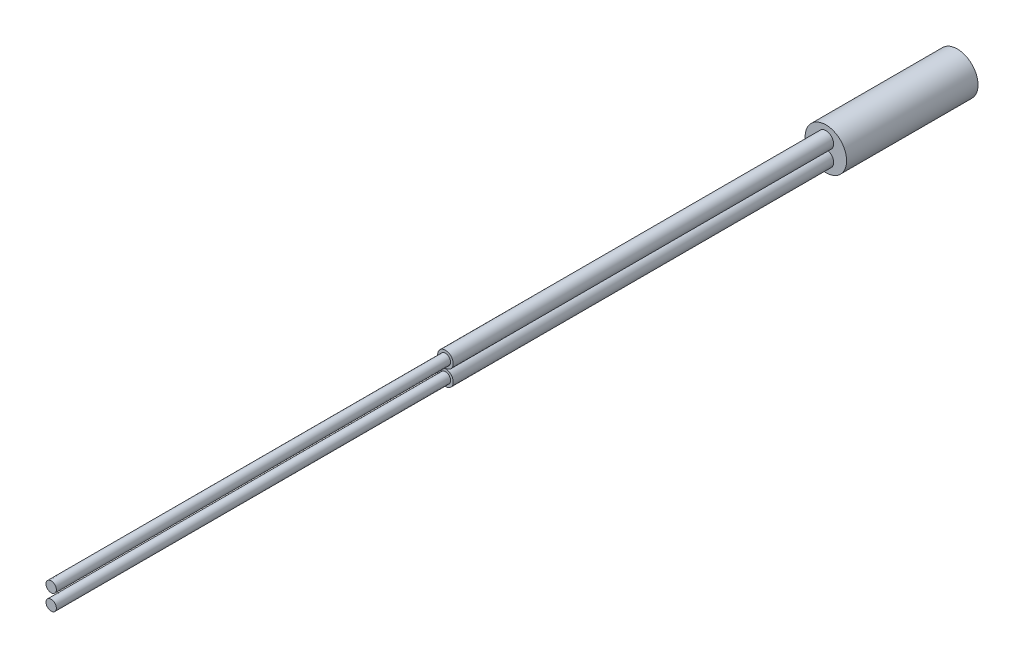
SolidWorks part; units mm, degrees
material "acero"
ref_plane "Alzado" through (0, 0, 0) normal (0, 0, 1) x (1, 0, 0)
ref_plane "Planta" through (0, 0, 0) normal (0, 1, 0) x (1, 0, 0)
ref_plane "Vista lateral" through (0, 0, 0) normal (1, 0, 0) x (0, 0, -1)
sketch "Croquis1" plane through (0, 0, 0) normal (0, 0, 1) x (1, 0, 0)
  circle A0 centre (0, 0) radius 3
  dimension "D1" = 6
extrude "Saliente-Extruir1" add sketch "Croquis1" along normal blind 18
ref_plane "Plano1" through (0, 0.5, 0) normal (0, -1, 0) x (-1, 0, 0)
ref_plane "Plano2" through (0, -9.5, 0) normal (0, -1, 0) x (-1, 0, 0)
ref_plane "Plano3" through (-23.0763, 0, 10.7606) normal (-0.9063, 0, 0.4226) x (0.4226, 0, 0.9063)
sketch3d "Croquis3D1"
  line L0 (0, 0, 18) -> (0, 0, 21)
  line L1 (0, 0, 18) -> (0, 0, 0) construction
  line L2 (-17.166, -4.6752, 23.4353) -> (-17.166, -8.5854, 23.4353)
  line L3 (-6.75, -14.9111, 10) -> (-6.75, 16.5741, 10) construction
  spline S0 degree 3 poles (0, 0, 21) (0, 0, 27.5004) (-12.019, 3.2907, 25.754) (-17.166, -2.2029, 23.4353) (-17.166, -4.6752, 23.4353) knots 0 0 0 0 0.663423 1 1 1 1
  dimension "D1" = 17
  dimension "D2" = 3
sketch "Croquis2" plane through (0, 0, 18) normal (0, 0, 1) x (1, 0, 0)
  circle A0 centre (0, 0) radius 0.8 construction
  circle A1 centre (-0.8, 0) radius 0.75
  circle A2 centre (0.8, 0) radius 0.75
  dimension "D1" = 1.6
  dimension "D2" = 1.5
sweep "Barrer1" [suppressed] add profiles "Croquis2" path "Croquis3D1"
extrude "Saliente-Extruir2" add sketch "Croquis1<2>" along normal blind 21.5 and the other way blind 1.5
sketch "Croquis1<2>" plane through (0, 0, 0) normal (0, 0, 1) x (1, 0, 0) same geometry as "Croquis1"
sketch "Croquis3" plane through (0, 0, -1.5) normal (0, 0, -1) x (-1, 0, 0)
  circle A0 centre (0, 0) radius 3
  dimension "D1" = 6
extrude "Cortar-Extruir1" cut sketch "Croquis3" against normal blind 4
sketch "Croquis4" plane through (0, 0, 0) normal (1, 0, 0) x (0, 0, -1)
  line L0 (-18.6464, 0) -> (-2.5, 0) construction
  line L1 (-2.5, -3) -> (-2.5, 3) construction
  line L2 (-2.5, 0) -> (8.1511, 15.6197) construction
  dimension "D1" = 34.29
sketch3d "Croquis3D4"
  line L0 (0, 0, 2.5) -> (-18.9322, 0, 2.5) construction
ref_plane "Plano4" through (0, 1.1637, 1.7065) normal (0, -0.5634, -0.8262) x (-1, 0, 0)
sketch3d "Croquis3D3" [suppressed]
  line L0 (-1.9716, 13.6377, 26.3138) -> (-2.2072, 8.1317, 30.0679)
  line L1 (-5.6206, 5.0135, 32.2682) -> (-41.5, -3.146, 34.1262)
  line L2 (-47.8249, -2.5398, 38.3697) -> (-47.8249, -22.8208, 52.1977)
  line L3 (-43.8249, -26.1257, 54.4511) -> (-27.8372, -26.1257, 54.4511)
  line L4 (-41, -0.2448, 33.0559) -> (-27.23, 0.0992, 33.3873)
  line L5 (-27.23, 0.0992, 33.3873) -> (-27.23, 3.5226, 33.3873)
  line L6 (-27.23, 3.5226, 33.3873) -> (-1.9922, 3.5226, 33.3873)
ref_plane "Plano5" through (0, 16.9384, 24.84) normal (0, -0.5634, -0.8262) x (-1, 0, 0)
sketch "Croquis6" plane through (0, 16.9384, 24.84) normal (0, -0.5634, -0.8262) x (-1, 0, 0)
  line L0 (0, -15.6127) -> (0, -12.1127) construction
  line L1 (22, -19.1127) -> (22, -15.6127)
  line L4 (22, -15.6127) -> (0, -15.6127)
  line L5 (47.5, -19.1127) -> (22, -19.1127)
  line L6 (47.5, -19.1127) -> (47.5, -50.6127)
  line L7 (47.5, -50.6127) -> (33.5, -50.6127)
  ellipse E0 centre (0, -12.1127) end of major axis (-3, -12.1127) minor radius 2.4786 construction
  dimension "D1" = 38.5
  dimension "D2" = 47.5
  dimension "D3" = 7
  dimension "D4" = 3.5
  dimension "D5" = 22
  dimension "D6" = 14
sketch3d "Croquis3D5"
  line L0 (0, 0, 21.5) -> (0, 4.0392, 33.6359) construction
  line L1 (0, 0, 21.5) -> (0, 0, 2.5) construction
  line L2 (-22, 3.2001, 34.2081) -> (-21.2499, 4.0392, 33.6359) construction
  line L3 (-47.5, -24.8777, 53.3543) -> (-33.5, -24.8777, 53.3543) construction
  line L4 (-47.5, 1.1475, 35.6078) -> (-47.5, -24.8777, 53.3543) construction
  line L5 (-44.5, -24.8777, 53.3543) -> (-47.5, -22.3991, 51.6641) construction
  line L6 (-46.4717, -0.2698, 36.5742) -> (-45.5, 1.1475, 35.6078) construction
  line L7 (-47.5, 1.1475, 35.6078) -> (-22, 1.1475, 35.6078) construction
  line L8 (-22, 1.1475, 35.6078) -> (-22, 4.0392, 33.6359) construction
  line L9 (-22.8792, 1.1475, 35.6078) -> (-22, 1.873, 35.113) construction
  line L10 (-22, 4.0392, 33.6359) -> (0, 4.0392, 33.6359) construction
  line L11 (-2, 4.0392, 33.6359) -> (0, 3.4076, 31.7383) construction
  arc A0 (-42.3787, -24.8777, 53.3543) -> (-47.5, -20.6465, 50.469) centre (-42.3787, -20.6465, 50.469) cw
  arc A1 (-47.5, -2.1436, 37.852) -> (-43.5165, 1.1475, 35.6078) centre (-43.5165, -2.1436, 37.852) cw
  arc A2 (-23.5, 1.1475, 35.6078) -> (-22, 2.3868, 34.7627) centre (-23.5, 2.3868, 34.7627) cw
  arc A4 (-3.4142, 4.0392, 33.6359) -> (0, 2.961, 30.3964) centre (-3.4142, 2.961, 30.3964) cw
  arc A5 (-22, 2.7999, 34.481) -> (-20.5, 4.0392, 33.6359) centre (-20.5, 2.7999, 34.481) cw
  point P7 (-42.3787, -23.5317, 46.2378)
  point P16 (-46, -23.6384, 52.5092)
  point P25 (-43.5165, -4.3879, 34.5608)
  point P27 (-45.9859, 0.4389, 36.091)
  point P29 (-23.5, 3.2319, 36.002)
  point P31 (-22.4396, 1.5102, 35.3604)
  point P44 (-20.5, 1.9548, 33.2417)
  point P46 (-21.625, 3.6196, 33.922)
  point P51 (-3.4142, 6.2005, 29.3182)
  point P53 (-1, 3.7234, 32.6871)
  dimension "D5" = 1.5
  dimension "D2" = 3
  dimension "D11" = 3
  dimension "D3" = 2
  dimension "D4" = 2
  dimension "D7" = 1.5
  dimension "D9" = 2
  dimension "D10" = 2
sketch3d "Croquis3D7"
  line L0 (-47.5, -24.8777, 53.3543) -> (-33.5, -24.8777, 53.3543) construction
  line L1 (-47.5, 1.1475, 35.6078) -> (-47.5, -24.8777, 53.3543) construction
  line L2 (-47.5, 1.1475, 35.6078) -> (-22, 1.1475, 35.6078) construction
  line L3 (-22, 1.1475, 35.6078) -> (-22, 4.0392, 33.6359) construction
  line L4 (-22, 4.0392, 33.6359) -> (0, 4.0392, 33.6359) construction
  line L5 (0, 0, 21.5) -> (0, 4.0392, 33.6359) construction
  line L6 (-42.3787, -24.8777, 53.3543) -> (-33.5, -24.8777, 53.3543)
  line L7 (-47.5, -2.1436, 37.852) -> (-47.5, -20.6465, 50.469)
  line L8 (-43.5165, 1.1475, 35.6078) -> (-23.5, 1.1475, 35.6078)
  line L9 (-22, 2.3868, 34.7627) -> (-22, 2.7999, 34.481)
  line L10 (-20.5, 4.0392, 33.6359) -> (-3.4142, 4.0392, 33.6359)
  line L11 (0, 0, 21.5) -> (0, 2.961, 30.3964)
  arc A0 (-42.3787, -24.8777, 53.3543) -> (-47.5, -20.6465, 50.469) centre (-42.3787, -20.6465, 50.469) ccw construction
  arc A1 (-47.5, -2.1436, 37.852) -> (-43.5165, 1.1475, 35.6078) centre (-43.5165, -2.1436, 37.852) ccw construction
  arc A2 (-23.5, 1.1475, 35.6078) -> (-22, 2.3868, 34.7627) centre (-23.5, 2.3868, 34.7627) ccw construction
  arc A4 (-3.4142, 4.0392, 33.6359) -> (0, 2.961, 30.3964) centre (-3.4142, 2.961, 30.3964) ccw construction
  arc A5 (-42.3787, -24.8777, 53.3543) -> (-47.5, -20.6465, 50.469) centre (-42.3787, -20.6465, 50.469) ccw
  arc A6 (-47.5, -2.1436, 37.852) -> (-43.5165, 1.1475, 35.6078) centre (-43.5165, -2.1436, 37.852) ccw
  arc A7 (-23.5, 1.1475, 35.6078) -> (-22, 2.3868, 34.7627) centre (-23.5, 2.3868, 34.7627) ccw
  arc A8 (-22, 2.7999, 34.481) -> (-20.5, 4.0392, 33.6359) centre (-20.5, 2.7999, 34.481) ccw construction
  arc A9 (-3.4142, 4.0392, 33.6359) -> (0, 2.961, 30.3964) centre (-3.4142, 2.961, 30.3964) ccw
  arc A10 (-22, 2.7999, 34.481) -> (-20.5, 4.0392, 33.6359) centre (-20.5, 2.7999, 34.481) ccw
  point P5 (-42.3787, -23.5317, 46.2378)
  point P10 (-43.5165, -4.3879, 34.5608)
  point P15 (-23.5, 3.2319, 36.002)
  point P20 (-20.5, 1.9548, 33.2417)
  point P25 (-3.4142, 6.2005, 29.3182)
  point P27 (-42.3787, -23.5317, 46.2378)
  point P28 (-43.5165, -4.3879, 34.5608)
  point P29 (-23.5, 3.2319, 36.002)
  point P31 (-3.4142, 6.2005, 29.3182)
  point P32 (-20.5, 1.9548, 33.2417)
ref_plane "Plano6" through (-33.5, -24.8777, 53.3543) normal (1, 0, 0) x (0, 0, -1)
sketch "Croquis7" plane through (-33.5, -24.8777, 53.3543) normal (1, 0, 0) x (0, 0, -1)
  line L0 (0.9708, -0.662) -> (-0.9708, 0.662) construction
  line L1 (17.7465, 26.0252) -> (0, 0) construction
  circle A0 centre (-0.9708, 0.662) radius 1.125
  circle A1 centre (0.9708, -0.662) radius 1.125
  dimension "D1" = 2.25
  dimension "D2" = 0.1
  dimension "D3" = 4.6
sweep "Barrer2" [suppressed] add profiles "Croquis7" path "Croquis3D7"
sketch "Croquis8" [suppressed] plane through (-33.5, 0, 0) normal (1, 0, 0) x (0, 0, -1)
  circle A0 centre (-54.6664, -23.983) radius 0.75
  circle A1 centre (-52.7248, -25.3069) radius 0.75
  dimension "D1" = 1.5
sketch3d "Croquis3D8" [suppressed]
  line L0 (-33.5, -25.3069, 52.7248) -> (-32.5, -25.3069, 52.7248)
  line L1 (-31.5, -25.8805, 51.9057) -> (-31.5, -26.6156, 50.8559) construction
  line L2 (-31.5, -25.3069, 52.7248) -> (-31.5, -25.3069, 45.2282) construction
  arc A0 (-32.5, -25.3069, 52.7248) -> (-31.5, -25.8805, 51.9057) centre (-32.5, -25.8805, 51.9057) ccw
  point P7 (-31.5, -25.3069, 52.7248)
  point P9 (-32.5, -25.0614, 51.3321)
  dimension "D3" = 1
  dimension "D1" = 2
  dimension "D2" = 1
  dimension "D5" = 1
  dimension "D4" = 35
sweep "Barrer3" [suppressed] add profiles "Croquis8" path "Croquis3D8"
sketch "Croquis9" plane through (0, 0, 21.5) normal (0, 0, 1) x (1, 0, 0)
  line L0 (0, 1.15) -> (0, -1.15) construction
  circle A0 centre (0, -1.15) radius 1.125
  circle A1 centre (0, 1.15) radius 1.125
  dimension "D1" = 2.25
  dimension "D2" = 2.3
extrude "Saliente-Extruir3" add sketch "Croquis9" along normal blind 55
sketch "Croquis10" plane through (0, 0, 21.5) normal (0, 0, 1) x (1, 0, 0)
  circle A0 centre (0, -1.15) radius 0.75
  circle A1 centre (0, 1.15) radius 0.75
  circle A2 centre (0, 1.15) radius 1.125 construction
  circle A3 centre (0, -1.15) radius 1.125 construction
  dimension "D1" = 1.5
extrude "Saliente-Extruir4" add sketch "Croquis10" along normal blind 112
